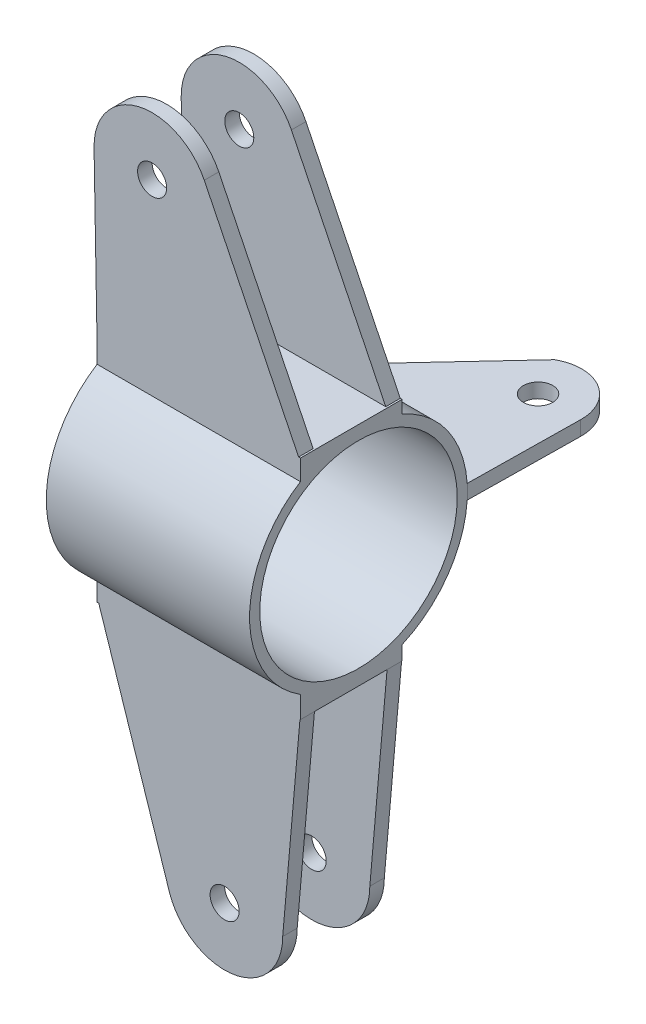
SolidWorks part; units mm, degrees
ref_plane "Front Plane" through (0, 0, 0) normal (0, 0, 1) x (1, 0, 0)
ref_plane "Top Plane" through (0, 0, 0) normal (0, 1, 0) x (1, 0, 0)
ref_plane "Right Plane" through (0, 0, 0) normal (1, 0, 0) x (0, 0, -1)
sketch "Sketch1" plane through (0, 0, 0) normal (1, 0, 0) x (0, 0, -1)
  circle A0 centre (0, 0) radius 37.5
  circle A1 centre (0, 0) radius 34
  dimension "D1" = 75
  dimension "D2" = 68
extrude "Boss-Extrude1" add sketch "Sketch1" along normal mid plane 70
sketch "Sketch2" plane through (0, 0, 0) normal (0, 0, 1) x (1, 0, 0)
  line L0 (-5.8, 94.5105) -> (-5.8, -74.5024) construction
  line L1 (35, -37.5) -> (35, 37.5) construction
  line L2 (-16.0528, 96.2387) -> (8.897, -106.9613) construction
  line L3 (-36.0464, 95.8804) -> (-35, 37.5)
  line L4 (1.9043, 105.0374) -> (35, 37.5)
  line L5 (35, 37.5) -> (-35, 37.5)
  line L8 (-35, -37.5) -> (35, -37.5)
  line L9 (-35, -37.5) -> (-10.1019, -113.2093)
  line L10 (35, -37.5) -> (28.897, -106.9613)
  circle A0 centre (-16.0528, 96.2387) radius 5
  circle A1 centre (8.897, -106.9613) radius 5
  arc A3 (-10.1019, -113.2093) -> (28.897, -106.9613) centre (8.897, -106.9613) ccw
  arc A4 (1.9043, 105.0374) -> (-36.0464, 95.8804) centre (-16.0528, 96.2387) ccw
  dimension "D3" = 10
  dimension "D4" = 10
  dimension "D7" = 40
  dimension "D1" = 40.8
  dimension "D2" = 7
  dimension "D5" = 203.2
extrude "Boss-Extrude2" add sketch "Sketch2" along normal blind 5 from offset 15 separate body
extrude "Boss-Extrude3" add sketch "Sketch2<2>" along normal blind 5 from offset 15 offset against normal yes
sketch "Sketch2<2>" plane through (0, 0, 0) normal (0, 0, 1) x (1, 0, 0) same geometry as "Sketch2"
sketch "Sketch3" plane through (35, 0, 0) normal (1, 0, 0) x (0, 0, -1)
  line L0 (-20, 37.5) -> (-20, 31.7214)
  line L2 (15, 37.5) -> (15, 34.3693)
  line L3 (-20, 38.7567) -> (15, 38.7567)
  line L4 (-15, 37.5) -> (-15, 105.0374)
  line L5 (-15, 105.0374) -> (-20, 105.0374)
  line L6 (-20, 105.0374) -> (-20, 37.5)
  line L7 (-20, 37.5) -> (-15, 37.5)
  line L10 (-20, 38.7567) -> (-20, 37.5)
  line L12 (15, 37.5) -> (15, 105.0374)
  line L13 (15, 105.0374) -> (10, 105.0374)
  line L14 (10, 105.0374) -> (10, 37.5)
  line L15 (10, 37.5) -> (15, 37.5)
  line L16 (15, 37.5) -> (15, 38.7567)
  circle A1 centre (0, 0) radius 37.5
  arc A2 (15, 34.3693) -> (-20, 31.7214) centre (0, 0) ccw
  dimension "D1" = 0
  dimension "D2" = 0
  dimension "D3" = 0
extrude "Boss-Extrude4" add sketch "Sketch3" against normal up to surface (70 mm away) up to face at (-35, 0, -37.5)
sketch "Sketch4" plane through (-35, 0, 0) normal (-1, 0, 0) x (0, 0, 1)
  line L32 (-15, -39.2326) -> (20, -39.2326)
  line L33 (-15, -34.3693) -> (-15, -39.2326)
  line L34 (20, -31.7214) -> (20, -39.2326)
  arc A0 (-15, 34.3693) -> (20, 31.7214) centre (0, 0) ccw construction
  arc A1 (-15, -34.3693) -> (20, -31.7214) centre (0, 0) ccw
extrude "Boss-Extrude5" add sketch "Sketch4" against normal up to surface (70 mm away) up to face at (35, 18.2914, 1.1678)
sketch "Sketch5" plane through (0, 0, 0) normal (0, 1, 0) x (1, 0, 0)
  line L0 (0, 0) -> (0, 125.568) construction
  line L1 (0, 0) -> (20.5399, 76.2831) construction
  line L2 (35, 37.5) -> (-35, 37.5)
  line L3 (-35, 37.5) -> (-35.0785, 37.5006)
  line L4 (13.1552, 89.3393) -> (-35.0785, 37.5006)
  line L5 (35.5341, 75.8655) -> (35, 37.5)
  circle A0 centre (20.5399, 76.2831) radius 5.05
  arc A1 (35.5341, 75.8655) -> (13.1552, 89.3393) centre (20.5399, 76.2831) ccw
  dimension "D3" = 10.1
  dimension "D4" = 30
  dimension "D1" = 15.07
  dimension "D2" = 79
extrude "Boss-Extrude6" add sketch "Sketch5" along normal mid plane 5 separate body
sketch "Sketch6" plane through (35, 0, 0) normal (1, 0, 0) x (0, 0, -1)
  line L3 (37.5, 2.5) -> (37.5, -2.5) construction
  line L13 (37.5, 2.5) -> (37.5, -2.5)
  line L23 (37.3501, 2.5) -> (37.3501, -2.5)
  line L24 (37.3501, -2.5) -> (37.5, -2.5)
  line L25 (37.5, 2.5) -> (37.3501, 2.5)
extrude "Boss-Extrude7" add sketch "Sketch6" against normal up to surface (70 mm away) up to face at (-35, 12.4207, 2.0833)
